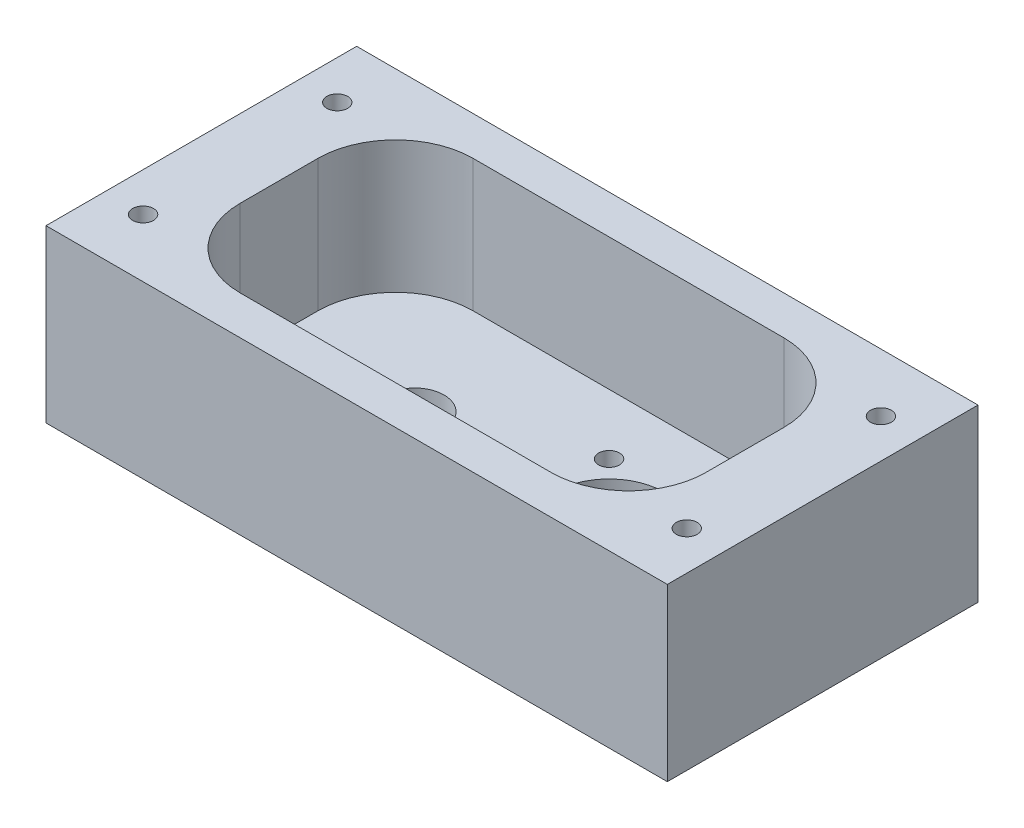
SolidWorks part; units mm, degrees
material "6061 Alloy"
ref_plane "Front Plane" through (0, 0, 0) normal (0, 0, 1) x (1, 0, 0)
ref_plane "Top Plane" through (0, 0, 0) normal (0, 1, 0) x (1, 0, 0)
ref_plane "Right Plane" through (0, 0, 0) normal (1, 0, 0) x (0, 0, -1)
sketch "Sketch1" plane through (0, 0, 0) normal (0, 1, 0) x (1, 0, 0)
  line L1 (-50.8, -25.4) -> (50.8, -25.4)
  line L2 (-50.8, -25.4) -> (-50.8, 25.4)
  line L3 (-50.8, 25.4) -> (50.8, 25.4)
  line L4 (50.8, -25.4) -> (50.8, 25.4)
  line L5 (-50.8, -25.4) -> (50.8, 25.4) construction
  line L6 (-50.8, 25.4) -> (50.8, -25.4) construction
  point P0 (0, 0)
  dimension "D1" = 101.6
  dimension "D2" = 50.8
extrude "Boss-Extrude1" add sketch "Sketch1" along normal blind 27.94
sketch "Sketch2" plane through (0, 0, 0) normal (0, -1, 0) x (1, 0, 0)
  line L0 (-50.8, 0) -> (50.8, 0) construction
  line L1 (-50.8, -25.4) -> (-50.8, 25.4) construction
  line L2 (50.8, 25.4) -> (50.8, -25.4) construction
  line L3 (0, 25.4) -> (0, -25.4) construction
  line L4 (-50.8, 25.4) -> (50.8, 25.4) construction
  line L5 (50.8, -25.4) -> (-50.8, -25.4) construction
  circle A0 centre (-15.875, 0) radius 4.7625
  circle A1 centre (15.875, 0) radius 9
  point P12 (-15.875, 0)
  point P13 (15.875, 0)
  dimension "D3" = 18
  dimension "D4" = 9.525
  dimension "D1" = 31.75
  dimension "D2" = 15.875
extrude "Cut-Extrude1" cut sketch "Sketch2" against normal through all contours A0 | A1
sketch "Sketch3" plane through (0, 27.94, 0) normal (0, 1, 0) x (1, 0, 0)
  line L0 (15.875, 0) -> (-15.875, 0) construction
  line L1 (-25.4, -19.05) -> (25.4, -19.05)
  line L2 (-38.1, -6.35) -> (-38.1, 6.35)
  line L3 (-25.4, 19.05) -> (25.4, 19.05)
  line L4 (38.1, -6.35) -> (38.1, 6.35)
  line L5 (-38.1, -19.05) -> (38.1, 19.05) construction
  line L6 (-38.1, 19.05) -> (38.1, -19.05) construction
  arc A0 (25.4, 19.05) -> (38.1, 6.35) centre (25.4, 6.35) cw
  arc A1 (38.1, -6.35) -> (25.4, -19.05) centre (25.4, -6.35) cw
  arc A2 (-25.4, -19.05) -> (-38.1, -6.35) centre (-25.4, -6.35) cw
  arc A3 (-38.1, 6.35) -> (-25.4, 19.05) centre (-25.4, 6.35) cw
  point P0 (0, 0)
  dimension "D3" = 12.7
  dimension "D1" = 38.1
  dimension "D2" = 76.2
extrude "Cut-Extrude2" cut sketch "Sketch3" against normal blind 21.59
sketch "Sketch4" plane through (0, 0, 0) normal (0, -1, 0) x (1, 0, 0)
  line L0 (-44.45, 25.4) -> (-44.45, -25.4) construction
  line L1 (-50.8, 25.4) -> (50.8, 25.4) construction
  line L2 (50.8, -25.4) -> (-50.8, -25.4) construction
  line L3 (44.45, 25.4) -> (44.45, -25.4) construction
  line L4 (-50.8, -25.4) -> (-50.8, 25.4) construction
  line L5 (50.8, 25.4) -> (50.8, -25.4) construction
  line L6 (-44.45, 0) -> (44.45, 0) construction
  line L7 (6.6826, 9.1924) -> (25.0674, -9.1924) construction
  line L8 (25.0674, 9.1924) -> (6.6826, -9.1924) construction
  circle A1 centre (15.875, 0) radius 9 construction
  point P12 (-44.45, 15.875)
  point P13 (-44.45, -15.875)
  point P14 (44.45, 15.875)
  point P15 (44.45, -15.875)
  point P20 (15.875, 0)
  point P25 (15.875, 0)
  point P27 (6.6826, 9.1924)
  point P28 (25.0674, 9.1924)
  point P29 (25.0674, -9.1924)
  point P30 (6.6826, -9.1924)
  dimension "D1" = 6.35
  dimension "D2" = 6.35
  dimension "D3" = 31.75
  dimension "D4" = 45
  dimension "D5" = 45
  dimension "D6" = 26
hole_wizard "M3 Clearance Hole1" positions "3DSketch1" profile "Sketch5" hole size "M3" standard "ANSI Metric" end condition through all
sketch3d "3DSketch1"
  point P0 (-44.45, 0, 15.875)
  point P3 (-44.45, 0, -15.875)
  point P6 (6.6826, 0, 9.1924)
  point P9 (6.6826, 0, -9.1924)
  point P12 (25.0674, 0, 9.1924)
  point P15 (25.0674, 0, -9.1924)
  point P18 (44.45, 0, 15.875)
  point P21 (44.45, 0, -15.875)
sketch "Sketch5" plane through (-44.45, 0, 15.875) normal (1, 0, 0) x (0, 0, -1)
  line L0 (0, 0) -> (0, 27.94)
  line L1 (0, 27.94) -> (1.7, 27.94)
  line L2 (1.7, 27.94) -> (1.7, 0)
  line L5 (1.7, 0) -> (0, 0)
  line L11 (0, -6.35) -> (0, 107.95) construction
  dimension "Thru Hole Dia." = 3.4
  dimension "Thru Hole Depth" = 27.94
equation "\"D2@Sketch4\"=\"D1@Sketch4\""
